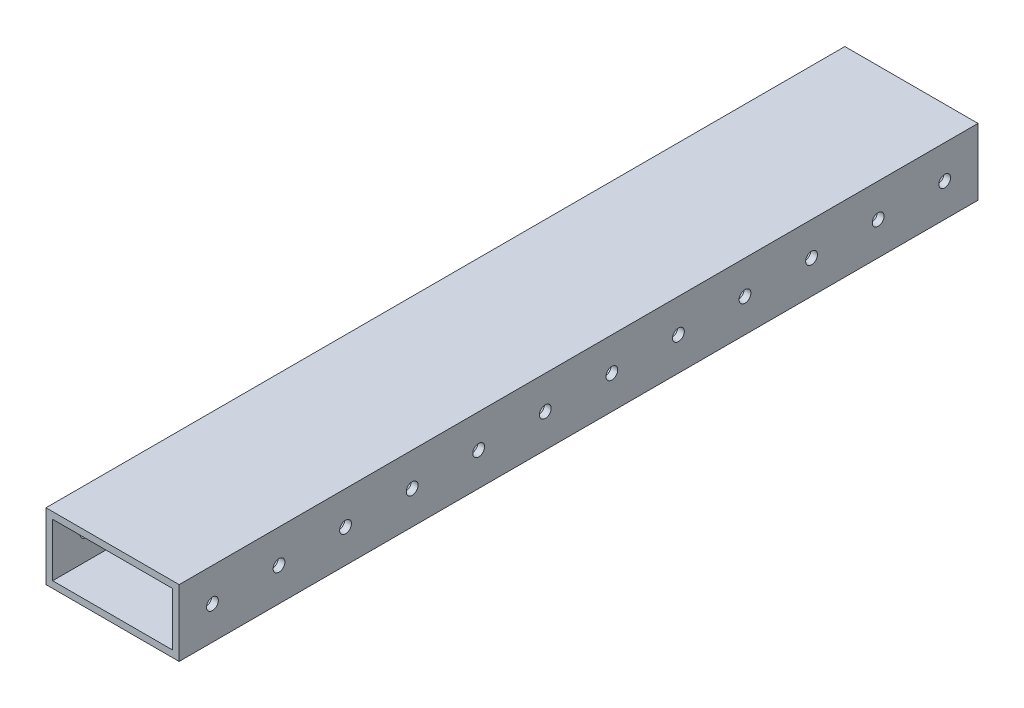
SolidWorks part; units mm, degrees
ref_plane "Front Plane" through (0, 0, 0) normal (0, 0, 1) x (1, 0, 0)
ref_plane "Top Plane" through (0, 0, 0) normal (0, 1, 0) x (1, 0, 0)
ref_plane "Right Plane" through (0, 0, 0) normal (1, 0, 0) x (0, 0, -1)
sketch "Sketch1" plane through (0, 0, 0) normal (0, 0, 1) x (1, 0, 0)
  line L1 (-25.4, -12.7) -> (25.4, -12.7)
  line L2 (-25.4, -12.7) -> (-25.4, 12.7)
  line L3 (-25.4, 12.7) -> (25.4, 12.7)
  line L4 (25.4, -12.7) -> (25.4, 12.7)
  line L5 (-25.4, -12.7) -> (25.4, 12.7) construction
  line L6 (-25.4, 12.7) -> (25.4, -12.7) construction
  line L7 (-22.86, -10.16) -> (22.86, -10.16)
  line L8 (-22.86, -10.16) -> (-22.86, 10.16)
  line L9 (-22.86, 10.16) -> (22.86, 10.16)
  line L10 (22.86, -10.16) -> (22.86, 10.16)
  line L11 (-22.86, -10.16) -> (22.86, 10.16) construction
  line L12 (-22.86, 10.16) -> (22.86, -10.16) construction
  point P0 (0, 0)
  point P6 (0, 0)
  dimension "D1" = 50.8
  dimension "D2" = 25.4
  dimension "D3" = 2.54
  dimension "D4" = 2.54
extrude "Boss-Extrude1" add sketch "Sketch1" against normal blind 533.4
hole_wizard "#8 Clearance Hole1" positions "Sketch2" profile "Sketch3" hole size "#8" standard "ANSI Inch" end condition through all
sketch "Sketch2" plane through (25.4, 0, 0) normal (1, 0, 0) x (0, 0, -1)
  line L0 (533.4, -12.7) -> (0, -12.7) construction
  point P0 (12.7, 0)
  point P16 (38.1, 0)
  point P17 (63.5, 0)
  point P18 (88.9, 0)
  point P19 (114.3, 0)
  point P20 (139.7, 0)
  point P21 (165.1, 0)
  point P22 (190.5, 0)
  point P23 (215.9, 0)
  point P24 (241.3, 0)
  point P25 (266.7, 0)
  point P26 (292.1, 0)
  point P27 (317.5, 0)
  point P28 (342.9, 0)
  point P29 (368.3, 0)
  point P30 (393.7, 0)
  point P31 (419.1, 0)
  point P32 (444.5, 0)
  point P33 (469.9, 0)
  point P34 (495.3, 0)
  point P35 (520.7, 0)
  dimension "D1" = 12.7
  dimension "D2" = 12.7
  dimension "D3" = 21
sketch "Sketch3" plane through (25.4, 0, -12.7) normal (0, 1, 0) x (0, 0, -1)
  line L0 (0, 0) -> (0, 50.8)
  line L1 (0, 50.8) -> (2.2479, 50.8)
  line L2 (2.2479, 50.8) -> (2.2479, 0)
  line L5 (2.2479, 0) -> (0, 0)
  line L11 (0, -6.35) -> (0, 107.95) construction
  dimension "Thru Hole Dia." = 4.4958
  dimension "Thru Hole Depth" = 50.8
sketch "Sketch4" plane through (0, 12.7, 0) normal (0, 1, 0) x (1, 0, 0)
  line L0 (-7.2063, 228.6) -> (135.5131, 228.6)
  line L3 (135.5131, 228.6) -> (135.5131, -17.6414)
  line L4 (135.5131, -17.6414) -> (-94.0569, -17.6414)
  line L5 (-94.0569, -17.6414) -> (-94.0569, 228.6)
  line L6 (-94.0569, 228.6) -> (-7.2063, 228.6)
extrude "Cut-Extrude2" cut sketch "Sketch4" against normal blind 76.962
ref_plane "Plane1" through (-25.4, 12.7, -533.4) normal (0, 0, 1) x (1, 0, 0)
